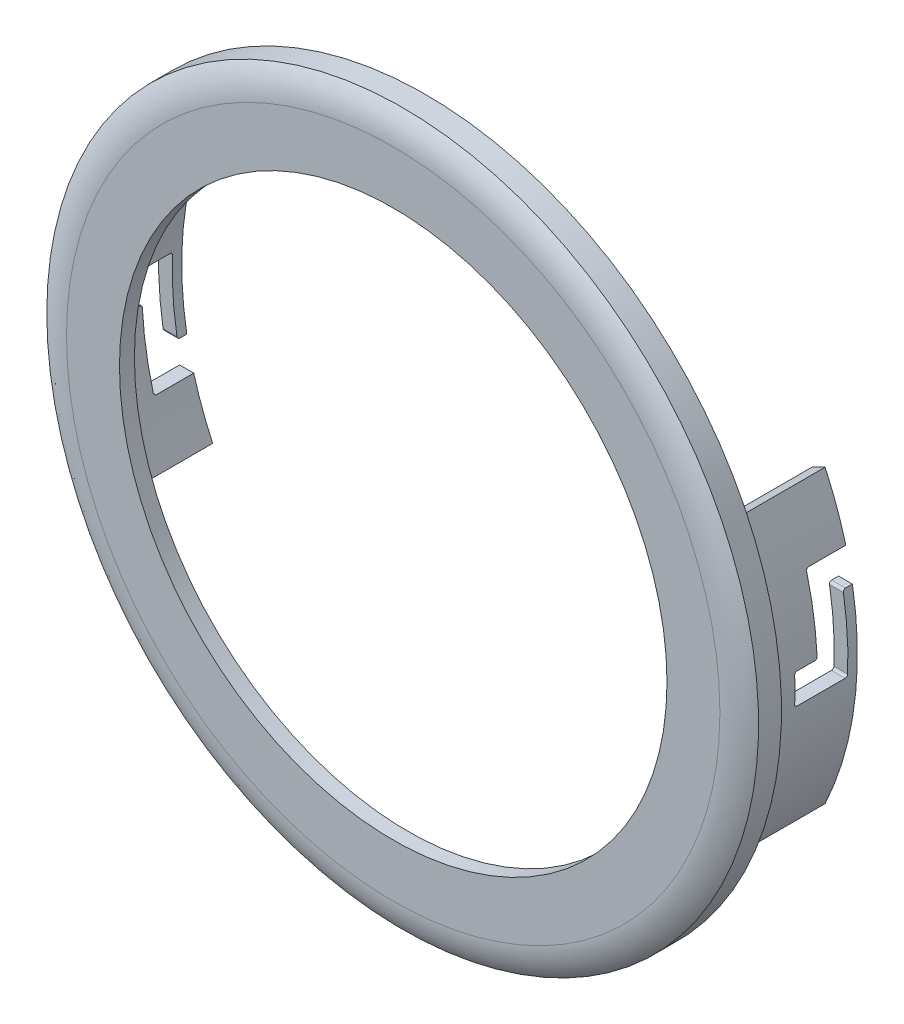
SolidWorks part; units mm, degrees
ref_plane "Alzado" through (0, 0, 0) normal (0, 0, 1) x (1, 0, 0)
ref_plane "Planta" through (0, 0, 0) normal (0, 1, 0) x (1, 0, 0)
ref_plane "Vista lateral" through (0, 0, 0) normal (1, 0, 0) x (0, 0, -1)
sketch "Croquis1" plane through (0, 0, 0) normal (0, 0, 1) x (1, 0, 0)
  circle A0 centre (0, 0) radius 75
  dimension "D1" = 150
extrude "Saliente-Extruir1" add sketch "Croquis1" against normal blind 6.5
sketch "Croquis2" plane through (0, 0, -6.5) normal (0, 0, -1) x (-1, 0, 0)
  circle A0 centre (0, 0) radius 69.25
  circle A1 centre (0, 0) radius 66.5
  dimension "D1" = 138.5
  dimension "D2" = 133
extrude "Saliente-Extruir2" add sketch "Croquis2" along normal blind 17.5
fillet "Redondeo1" radius 10 1 edges at (75, 0, 0)
sketch "Croquis5" plane through (0, 0, -6.5) normal (0, 0, -1) x (-1, 0, 0)
  circle A0 centre (0, 0) radius 60
  dimension "D1" = 120
extrude "Cortar-Extruir2" cut sketch "Croquis5" against normal blind 121.5
sketch "Croquis6" plane through (0, 0, -6.5) normal (0, 0, -1) x (-1, 0, 0)
  line L0 (0, 0) -> (-76.1004, 35.4862)
  line L1 (0, 0) -> (76.1004, 35.4862)
  line L2 (0, 3.575) -> (0, -3.575) construction
  line L3 (3.575, 0) -> (-3.575, 0) construction
  circle A0 centre (0, 0) radius 53.7954
  arc A1 (76.1004, 35.4862) -> (-76.1004, 35.4862) centre (0, 0) ccw
  circle M1 centre (0, 0) radius 60
  circle M2 centre (0, 0) radius 66.5
  dimension "D1" = 130
  dimension "D2" = 65
  dimension "D3" = 0
  dimension "D4" = 0
extrude "Cortar-Extruir3" cut sketch "Croquis6" along normal blind 121.5 contours A0 L1 L0 M1 | L1 A1 L0 M2 | L1 L0 M1 M2
sketch "Croquis7" plane through (0, 0, -6.5) normal (0, 0, -1) x (-1, 0, 0)
  circle A0 centre (0, 0) radius 63
  circle A1 centre (0, 0) radius 60
  dimension "D1" = 126
extrude "Cortar-Extruir4" cut sketch "Croquis7" against normal blind 1.5 from offset 2 offset against normal yes
sketch "Croquis8" plane through (0, 0, -6.5) normal (0, 0, -1) x (-1, 0, 0)
  line L1 (59.7766, 19.8937) -> (-54.9202, -30.8671)
  line L2 (54.9202, 30.8671) -> (-59.7766, -19.8937)
  arc A0 (59.7766, 19.8937) -> (54.9202, 30.8671) centre (0, 0) ccw
  arc A1 (-59.7766, -19.8937) -> (-54.9202, -30.8671) centre (0, 0) ccw
  dimension "D1" = 126
extrude "Cortar-Extruir5" cut sketch "Croquis8" against normal up to surface (3.5 mm away) up to face at (-60, 0, -3)
sketch "Croquis9" plane through (0, 0, 0) normal (0, 0, 1) x (1, 0, 0)
  circle A0 centre (0, 0) radius 65.6325
  circle A1 centre (0, 0) radius 55
  dimension "D1" = 110
extrude "Saliente-Extruir3" add sketch "Croquis9" against normal up to surface (3 mm away) up to face at (-60, 0, -3)
mirror "Simetría1" about plane through (0, 0, 0) normal (0, 1, 0) of "Cortar-Extruir3"
sketch "Croquis10" plane through (0, 0, 0) normal (1, 0, 0) x (0, 0, -1)
  line L0 (24, -29.2663) -> (24, 29.2663) construction
  line L1 (24, -17.7852) -> (16.5, -17.7852)
  line L2 (24, -17.7852) -> (24, -11.6852)
  line L3 (24, -11.6852) -> (22.6, -11.6852)
  line L4 (16, -17.2852) -> (16, -11.6852)
  line L5 (13.2, 0) -> (-13.2, 0) construction
  line L6 (16.5, -17.7852) -> (20.1, -17.7852)
  line L7 (16, -17.2852) -> (16, -3.55)
  line L8 (11.95, 3.05) -> (21.6, 3.05)
  line L9 (22.1, -11.1852) -> (22.1, 2.55)
  line L10 (6.5, -75) -> (6.5, 75) construction
  line L11 (21.6, 3.05) -> (11.95, 3.05)
  line L12 (22.1, 2.55) -> (22.1, -3.05)
  line L13 (15.5, -3.05) -> (11.95, -3.05)
  line L14 (11.45, 2.55) -> (11.45, -2.55)
  arc A0 (11.95, 3.05) -> (11.45, 2.55) centre (11.95, 2.55) ccw
  arc A1 (11.45, -2.55) -> (11.95, -3.05) centre (11.95, -2.55) ccw
  arc A2 (15.5, -3.05) -> (16, -3.55) centre (15.5, -3.55) cw
  arc A3 (21.6, 3.05) -> (22.1, 2.55) centre (21.6, 2.55) cw
  arc A4 (22.1, -11.1852) -> (22.6, -11.6852) centre (22.6, -11.1852) ccw
  arc A5 (16, -17.2852) -> (16.5, -17.7852) centre (16.5, -17.2852) ccw
  dimension "D7" = 0.5
  dimension "D1" = 3.05
  dimension "D2" = 8
  dimension "D3" = 6.1
  dimension "D5" = 6.1
  dimension "D6" = 4.95
extrude "Cortar-Extruir7" cut sketch "Croquis10" against normal blind 90 contours L4 A5 L1 L2 L3 A4 L9 A3 L8 A0 L14 A1 L13 A2 L7
pattern_circular "MatrizC1" count 2 over 360 of "Cortar-Extruir7"
sketch "Croquis11" plane through (0, 0, -6.5) normal (0, 0, -1) x (-1, 0, 0)
  circle A0 centre (0, 0) radius 71.5
  dimension "D1" = 143
extrude "Cortar-Extruir8" cut sketch "Croquis11" against normal blind 61 flip side to cut
scale "Escala1" scale about centroid uniform scaling yes scale factor 0.8
